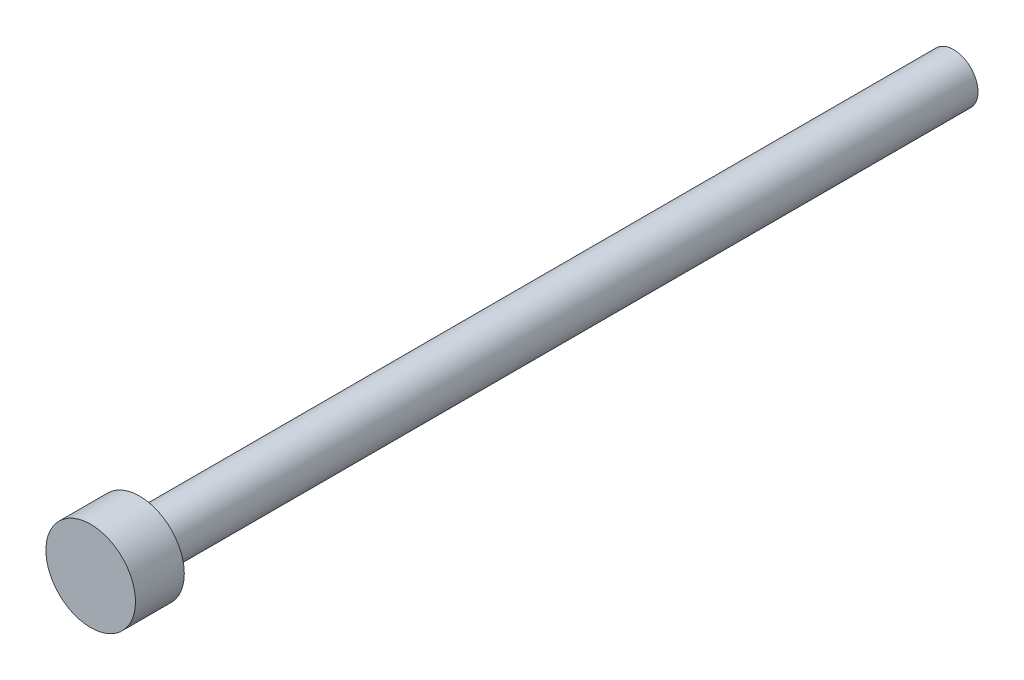
SolidWorks part; units mm, degrees
ref_plane "Front Plane" through (0, 0, 0) normal (0, 0, 1) x (1, 0, 0)
ref_plane "Top Plane" through (0, 0, 0) normal (0, 1, 0) x (1, 0, 0)
ref_plane "Right Plane" through (0, 0, 0) normal (1, 0, 0) x (0, 0, -1)
sketch "Shank_nominal_thread_envelope_profile" plane through (0, 0, 0) normal (0, 0, 1) x (1, 0, 0)
  circle A0 centre (0, 0) radius 1.5
  dimension "D1" = 3
extrude "Shank_nominal_thread_envelope" add sketch "Shank_nominal_thread_envelope_profile" along normal blind 50 from offset 50 offset against normal yes
sketch "Socket_head_envelope_profile" plane through (0, 0, 0) normal (0, 0, 1) x (1, 0, 0)
  circle A0 centre (0, 0) radius 2.75
  dimension "D1" = 5.5
extrude "Socket_head_envelope" add sketch "Socket_head_envelope_profile" along normal blind 3
